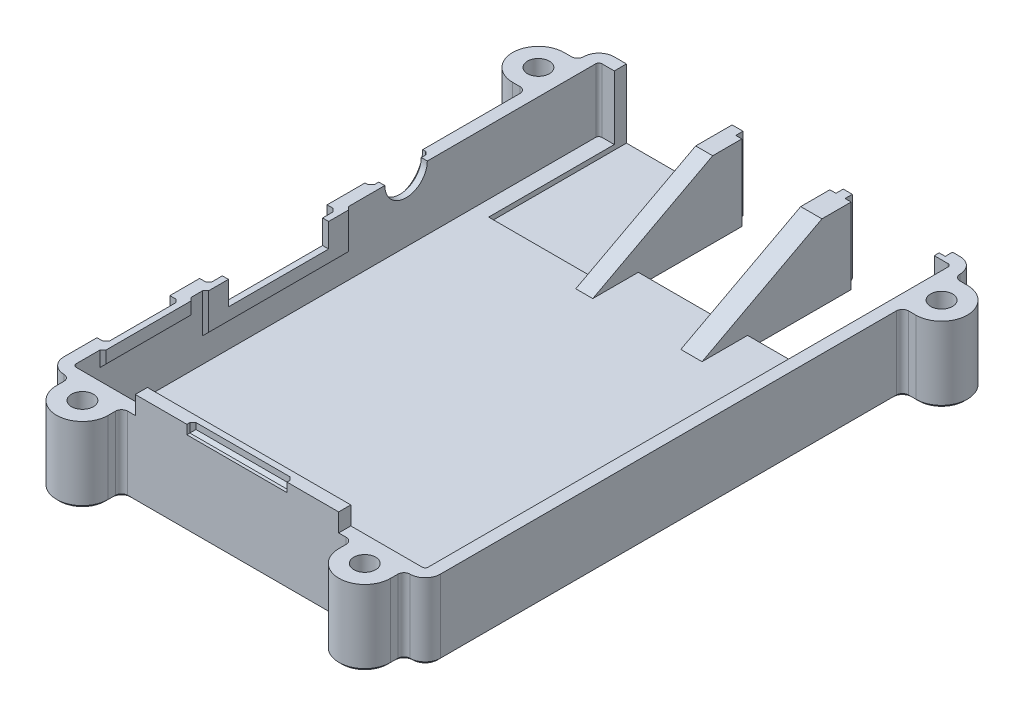
SolidWorks part; units mm, degrees
ref_plane "Front Plane" through (0, 0, 0) normal (0, 0, 1) x (1, 0, 0)
ref_plane "Top Plane" through (0, 0, 0) normal (0, 1, 0) x (1, 0, 0)
ref_plane "Right Plane" through (0, 0, 0) normal (1, 0, 0) x (0, 0, -1)
sketch "Sketch2" plane through (0, 0, 0) normal (0, 1, 0) x (1, 0, 0)
  line L1 (2.5, 0) -> (59.5, 0)
  line L2 (0, 2.5) -> (0, 88.1)
  line L3 (2.5, 90.6) -> (59.5, 90.6)
  line L4 (62, 2.5) -> (62, 88.1)
  arc A0 (0, 2.5) -> (2.5, 0) centre (2.5, 2.5) ccw
  arc A1 (59.5, 0) -> (62, 2.5) centre (59.5, 2.5) ccw
  arc A2 (62, 88.1) -> (59.5, 90.6) centre (59.5, 88.1) ccw
  arc A3 (2.5, 90.6) -> (0, 88.1) centre (2.5, 88.1) ccw
  point P7 (0, 0)
  point P10 (62, 0)
  point P13 (62, 90.6)
  point P16 (0, 90.6)
  dimension "D3" = 2.5
  dimension "D1" = 62
  dimension "D2" = 90.6
extrude "Base" add sketch "Sketch2" along normal blind 12.5
shell "Shell" thickness 2 removed face at (31, 12.5, -45.3)
sketch "Sketch14" plane through (0, 0, 0) normal (0, -1, 0) x (1, 0, 0)
  line L0 (31, 0) -> (31, -90.6) construction
  line L2 (59.5, -90.6) -> (2.5, -90.6) construction
  line L3 (-2.2, -78.6) -> (0, -78.6)
  line L4 (0, -88.1) -> (0, -2.5) construction
  line L5 (0, -78.6) -> (0, -87.1)
  line L6 (0, -87.1) -> (-2.2, -87.1)
  line L7 (3.5, 2.2) -> (3.5, 0)
  line L8 (2.5, 0) -> (59.5, 0) construction
  line L9 (3.5, 0) -> (12, 0)
  line L10 (12, 0) -> (12, 2.2)
  line L11 (64.2, -78.6) -> (62, -78.6)
  line L12 (62, -87.1) -> (64.2, -87.1)
  line L13 (62, -78.6) -> (62, -87.1)
  line L14 (50, 0) -> (50, 2.2)
  line L15 (58.5, 0) -> (50, 0)
  line L16 (58.5, 2.2) -> (58.5, 0)
  line L17 (2.5, 0) -> (59.5, 0) construction
  arc A0 (-2.2, -78.6) -> (-2.2, -87.1) centre (-2.2, -82.85) ccw
  arc A1 (3.5, 2.2) -> (12, 2.2) centre (7.75, 2.2) cw
  arc A2 (64.2, -78.6) -> (64.2, -87.1) centre (64.2, -82.85) cw
  arc A3 (58.5, 2.2) -> (50, 2.2) centre (54.25, 2.2) ccw
  dimension "D1" = 2.2
  dimension "D2" = 8.5
  dimension "D3" = 3.5
  dimension "D4" = 3.5
extrude "Clamps" add sketch "Sketch14" against normal up to surface (12.5 mm away) up to face at (31, 12.5, -45.3)
fillet "Clamp Fillets" radius 1 8 edges at (50, 6.25, 0) (58.5, 6.25, 0) (12, 6.25, 0) (3.5, 6.25, 0) (0, 6.25, -87.1) (0, 6.25, -78.6) (62, 6.25, -78.6) (62, 6.25, -87.1)
sketch "Sketch20" plane through (0, 0, 0) normal (0, -1, 0) x (1, 0, 0)
  circle A0 centre (7.75, 2.2) radius 1.8
  circle A1 centre (54.25, 2.2) radius 1.8
  circle A2 centre (64.2, -82.85) radius 1.8
  circle A3 centre (-2.2, -82.85) radius 1.8
  arc A4 (12, 2.2) -> (3.5, 2.2) centre (7.75, 2.2) ccw construction
  arc A5 (58.5, 2.2) -> (50, 2.2) centre (54.25, 2.2) ccw construction
  arc A6 (-2.2, -78.6) -> (-2.2, -87.1) centre (-2.2, -82.85) ccw construction
  arc A7 (64.2, -87.1) -> (64.2, -78.6) centre (64.2, -82.85) ccw construction
  dimension "D1" = 3.6
extrude "Clamp Holes" cut sketch "Sketch20" against normal through all
sketch "Sketch21" plane through (0, 0, 0) normal (0, -1, 0) x (1, 0, 0)
  circle A0 centre (7.75, 2.2) radius 2.9
  circle A1 centre (54.25, 2.2) radius 2.9
  circle A2 centre (64.2, -82.85) radius 2.9
  circle A3 centre (-2.2, -82.85) radius 2.9
  circle A4 centre (-2.2, -82.85) radius 1.8 construction
  circle A5 centre (7.75, 2.2) radius 1.8 construction
  circle A6 centre (54.25, 2.2) radius 1.8 construction
  circle A7 centre (64.2, -82.85) radius 1.8 construction
  dimension "D1" = 5.8
extrude "Clamp Countersinks" cut sketch "Sketch21" against normal blind 3.4
chamfer "Clamp Countersink Chamfers" distance 0.3 angle 45 4 edges at (-2.2, 0, -85.75) (64.2, 0, -85.75) (54.25, 0, -0.7) (7.75, 0, -0.7)
sketch "Sketch22" plane through (0, 12.5, 0) normal (0, 1, 0) x (1, 0, 0)
  line L0 (31, 2) -> (31, 0) construction
  line L1 (2.5, 2) -> (59.5, 2) construction
  line L2 (13, 0) -> (49, 0) construction
  line L4 (14.25, 2) -> (47.75, 2)
  line L5 (14.25, 2) -> (14.25, 0)
  line L6 (14.25, 0) -> (47.75, 0)
  line L7 (47.75, 2) -> (47.75, 0)
  dimension "D1" = 16.75
  dimension "D2" = 33.5
extrude "SD Fill" add sketch "Sketch22" along normal blind 3
sketch "Sketch23" plane through (0, 0, 0) normal (0, 0, 1) x (1, 0, 0)
  line L0 (31, 15.5) -> (31, 0) construction
  line L1 (14.25, 15.5) -> (47.75, 15.5) construction
  line L2 (13, 0) -> (49, 0) construction
  line L4 (22.75, 15.5) -> (39.25, 15.5)
  line L5 (22.75, 15.5) -> (22.75, 14)
  line L6 (22.75, 14) -> (39.25, 14)
  line L7 (39.25, 15.5) -> (39.25, 14)
  dimension "D1" = 8.25
  dimension "D2" = 16.5
  dimension "D3" = 1.5
extrude "SD Approach" cut sketch "Sketch23" against normal blind 1
chamfer "SD Approach Chamfer" distance 0.5 angle 45 3 edges at (39.25, 14.75, -1) (31, 14, -1) (22.75, 14.75, -1)
sketch "Sketch24" plane through (0, 0, -90.6) normal (0, 0, -1) x (-1, 0, 0)
  line L0 (-59.5, 12.5) -> (-2.5, 12.5) construction
  line L1 (-57.25, 12.5) -> (-42.75, 12.5)
  line L2 (-57.25, 12.5) -> (-57.25, 0)
  line L3 (-57.25, 0) -> (-42.75, 0)
  line L4 (-42.75, 12.5) -> (-42.75, 0)
  line L5 (-59.5, 0) -> (-2.5, 0) construction
  line L6 (0, 12.5) -> (0, 0) construction
  line L7 (-39.25, 12.5) -> (-24.75, 12.5)
  line L8 (-39.25, 12.5) -> (-39.25, 0)
  line L9 (-39.25, 0) -> (-24.75, 0)
  line L10 (-24.75, 12.5) -> (-24.75, 0)
  dimension "D1" = 14.5
  dimension "D2" = 24.75
  dimension "D3" = 42.75
extrude "USB Cutout" cut sketch "Sketch24" against normal blind 18.25
sketch "Sketch25" plane through (0, 0, -90.6) normal (0, 0, -1) x (-1, 0, 0)
  line L0 (-42.75, 12.5) -> (-39.25, 12.5) construction
  line L1 (-41.75, 12.5) -> (-58.25, 12.5)
  line L2 (-41.75, 12.5) -> (-41.75, 0)
  line L3 (-41.75, 0) -> (-58.25, 0)
  line L4 (-58.25, 12.5) -> (-58.25, 0)
  line L5 (-59.5, 0) -> (-57.25, 0) construction
  line L6 (-24.75, 12.5) -> (-2.5, 12.5) construction
  line L7 (-23.75, 12.5) -> (-40.25, 12.5)
  line L8 (-23.75, 12.5) -> (-23.75, 0)
  line L9 (-23.75, 0) -> (-40.25, 0)
  line L10 (-40.25, 12.5) -> (-40.25, 0)
  line L11 (-42.75, 0) -> (-39.25, 0) construction
  line L12 (-57.25, 12.5) -> (-57.25, 0) construction
  line L13 (-42.75, 0) -> (-42.75, 12.5) construction
  line L14 (-39.25, 12.5) -> (-39.25, 0) construction
  line L15 (-24.75, 0) -> (-24.75, 12.5) construction
  point P18 (-57.25, 6.25)
  dimension "D1" = 1
  dimension "D2" = 1
  dimension "D3" = 1
  dimension "D4" = 1
extrude "USB Approach" cut sketch "Sketch25" against normal blind 1.2
sketch "Sketch26" plane through (42.75, 0, 0) normal (1, 0, 0) x (0, 0, -1)
  line L0 (88.6, 2) -> (88.6, 12.5)
  line L1 (88.6, 12.5) -> (84.6, 12.5)
  line L2 (88.6, 2) -> (64.8524, 2)
  line L3 (64.8524, 2) -> (84.6, 12.5)
  line L4 (90.6, 0) -> (90.6, 12.5) construction
  dimension "D1" = 6
  dimension "D2" = 28
extrude "USB Inner Support" add sketch "Sketch26" against normal up to surface (3.5 mm away) up to face at (39.25, 4.8333, -83.45)
sketch "Sketch27" plane through (24.75, 0, 0) normal (1, 0, 0) x (0, 0, -1)
  line L0 (88.6, 2) -> (88.6, 12.5)
  line L1 (88.6, 12.5) -> (84.6, 12.5)
  line L2 (88.6, 2) -> (64.8524, 2)
  line L3 (64.8524, 2) -> (84.6, 12.5)
  line L4 (90.6, 0) -> (90.6, 12.5) construction
  dimension "D1" = 6
  dimension "D2" = 28
extrude "USB Outer Support" add sketch "Sketch27" against normal blind 2.8
sketch "Sketch28" plane through (0, 0, -90.6) normal (0, 0, -1) x (-1, 0, 0)
  line L0 (-23.75, 12.5) -> (-2.5, 12.5) construction
  line L1 (-21.95, 12.5) -> (-4.55, 12.5)
  line L2 (-21.95, 12.5) -> (-21.95, 1.2)
  line L3 (-21.95, 1.2) -> (-4.55, 1.2)
  line L4 (-4.55, 12.5) -> (-4.55, 1.2)
  line L5 (0, 12.5) -> (0, 0) construction
  dimension "D1" = 17.4
  dimension "D2" = 4.55
  dimension "D3" = 11.3
extrude "RJ45 Cutout" cut sketch "Sketch28" against normal blind 22.7
sketch "Sketch29" plane through (2, 0, 0) normal (1, 0, 0) x (0, 0, -1)
  line L0 (88.1, 12.5) -> (2.5, 12.5) construction
  line L1 (6.45, 12.5) -> (21.45, 12.5)
  line L2 (6.45, 12.5) -> (6.45, 10)
  line L3 (6.45, 10) -> (21.45, 10)
  line L4 (21.45, 12.5) -> (21.45, 10)
  line L5 (0, 12.5) -> (0, 0) construction
  line L6 (23.35, 12.5) -> (47.35, 12.5)
  line L7 (23.35, 12.5) -> (23.35, 6.07)
  line L8 (23.35, 6.07) -> (47.35, 6.07)
  line L9 (47.35, 12.5) -> (47.35, 6.07)
  dimension "D1" = 24
  dimension "D2" = 15
  dimension "D3" = 6.45
  dimension "D4" = 23.35
  dimension "D5" = 2.5
  dimension "D6" = 6.43
extrude "HDMI Support" add sketch "Sketch29" along normal blind 0.5
chamfer "HDMI Support Chamfer" distance 0.5 angle 45 6 edges at (2.5, 9.285, -47.35) (2.5, 6.07, -35.35) (2.5, 9.285, -23.35) (2.5, 11.25, -21.45) (2.5, 10, -13.95) (2.5, 11.25, -6.45)
sketch "Sketch30" plane through (0, 0, 0) normal (-1, 0, 0) x (0, 0, 1)
  line L0 (-77.6, 12.5) -> (-2.5, 12.5) construction
  line L1 (-24.85, 12.5) -> (-45.85, 12.5)
  line L2 (-24.85, 12.5) -> (-24.85, 6.57)
  line L3 (-24.85, 6.57) -> (-45.85, 6.57)
  line L4 (-45.85, 12.5) -> (-45.85, 6.57)
  line L5 (0, 12.5) -> (0, 0) construction
  line L6 (-19.95, 12.5) -> (-7.95, 12.5)
  line L7 (-19.95, 12.5) -> (-19.95, 10.5)
  line L8 (-19.95, 10.5) -> (-7.95, 10.5)
  line L9 (-7.95, 12.5) -> (-7.95, 10.5)
  dimension "D1" = 12
  dimension "D2" = 21
  dimension "D3" = 7.95
  dimension "D4" = 24.85
  dimension "D5" = 5.93
  dimension "D6" = 2
extrude "HDMI Approach" cut sketch "Sketch30" against normal blind 1.5
sketch "Sketch31" plane through (1.5, 0, 0) normal (-1, 0, 0) x (0, 0, 1)
  line L0 (-24.85, 12.5) -> (-45.85, 12.5) construction
  line L1 (-43.6, 12.5) -> (-27.1, 12.5)
  line L2 (-43.6, 12.5) -> (-43.6, 8.57)
  line L3 (-43.6, 8.57) -> (-27.1, 8.57)
  line L4 (-27.1, 12.5) -> (-27.1, 8.57)
  line L5 (-45.85, 12.5) -> (-45.85, 6.57) construction
  line L6 (-24.85, 6.57) -> (-24.85, 12.5) construction
  line L7 (-45.85, 6.57) -> (-24.85, 6.57) construction
  dimension "D1" = 2.25
  dimension "D2" = 2.25
  dimension "D3" = 2
extrude "HDMI Cutout" cut sketch "Sketch31" against normal blind 1
chamfer "HDMI Approach Chamfer" distance 0.5 angle 45 6 edges at (1.5, 11.5, -7.95) (1.5, 10.5, -13.95) (1.5, 11.5, -19.95) (1.5, 9.535, -24.85) (1.5, 6.57, -35.35) (1.5, 9.535, -45.85)
sketch "Sketch32" plane through (0, 0, 0) normal (-1, 0, 0) x (0, 0, 1)
  line L0 (-77.6, 12.5) -> (-45.85, 12.5) construction
  line L1 (0, 12.5) -> (0, 0) construction
  circle A0 centre (-56.85, 12.5) radius 3.5
  dimension "D1" = 7
  dimension "D2" = 56.85
extrude "Audio Cutout" cut sketch "Sketch32" against normal blind 2
sketch "Sketch33" plane through (0, 0, 0) normal (-1, 0, 0) x (0, 0, 1)
  circle A0 centre (-56.85, 12.5) radius 4.75
  arc A1 (-60.35, 12.5) -> (-53.35, 12.5) centre (-56.85, 12.5) ccw construction
  dimension "D1" = 9.5
extrude "Audio Approach" cut sketch "Sketch33" against normal blind 1
chamfer "Audio Approach Chamfer" distance 0.5 angle 45 1 edges at (1, 7.75, -56.85)
sketch "Sketch34" plane through (0, 0, 0) normal (0, -1, 0) x (1, 0, 0)
  line L0 (62, -2.5) -> (62, -77.6) construction
  line L1 (52.5, -9.4) -> (58.5, -9.4)
  line L2 (52.5, -9.4) -> (52.5, -62.1)
  line L3 (52.5, -62.1) -> (58.5, -62.1)
  line L4 (58.5, -9.4) -> (58.5, -62.1)
  line L5 (13, 0) -> (49, 0) construction
  point P6 (55.5, -9.4)
  dimension "D1" = 6
  dimension "D2" = 52.7
  dimension "D3" = 3.5
  dimension "D4" = 9.4
extrude "Header Cutout" cut sketch "Sketch34" against normal blind 2
sketch "Sketch35" plane through (0, 0, 0) normal (0, -1, 0) x (1, 0, 0)
  line L0 (55.5, -9.4) -> (55.5, -62.1) construction
  line L1 (58.5, -9.4) -> (52.5, -9.4) construction
  line L2 (52.5, -62.1) -> (58.5, -62.1) construction
  line L3 (52.5, -35.75) -> (58.5, -35.75) construction
  line L4 (52.5, -9.4) -> (52.5, -62.1) construction
  line L5 (58.5, -62.1) -> (58.5, -9.4) construction
  line L6 (56, -9.4) -> (55, -9.4)
  line L7 (55, -9.4) -> (55, -10.4)
  line L8 (55, -10.4) -> (53.5, -10.4)
  line L9 (53.5, -10.4) -> (53.5, -15.3625)
  line L10 (53.5, -15.3625) -> (52.5, -15.3625)
  line L11 (52.5, -15.3625) -> (52.5, -16.3625)
  line L12 (52.5, -16.3625) -> (53.5, -16.3625)
  line L13 (53.5, -16.3625) -> (53.5, -28.2875)
  line L14 (53.5, -28.2875) -> (52.5, -28.2875)
  line L15 (52.5, -28.2875) -> (52.5, -29.2875)
  line L16 (52.5, -29.2875) -> (53.5, -29.2875)
  line L17 (53.5, -29.2875) -> (53.5, -34.25)
  line L18 (53.5, -34.25) -> (55, -34.25)
  line L19 (55, -34.25) -> (55, -35.25)
  line L20 (55, -35.25) -> (52.5, -35.25)
  line L21 (52.5, -35.25) -> (52.5, -36.25)
  line L22 (56, -62.1) -> (55, -62.1)
  line L23 (55, -36.25) -> (52.5, -36.25)
  line L24 (55, -37.25) -> (55, -36.25)
  line L25 (53.5, -37.25) -> (55, -37.25)
  line L26 (53.5, -42.2125) -> (53.5, -37.25)
  line L27 (52.5, -42.2125) -> (53.5, -42.2125)
  line L28 (52.5, -43.2125) -> (52.5, -42.2125)
  line L29 (53.5, -43.2125) -> (52.5, -43.2125)
  line L30 (53.5, -55.1375) -> (53.5, -43.2125)
  line L31 (52.5, -55.1375) -> (53.5, -55.1375)
  line L32 (52.5, -56.1375) -> (52.5, -55.1375)
  line L33 (53.5, -56.1375) -> (52.5, -56.1375)
  line L34 (53.5, -61.1) -> (53.5, -56.1375)
  line L35 (55, -61.1) -> (53.5, -61.1)
  line L36 (55, -62.1) -> (55, -61.1)
  line L37 (56, -62.1) -> (56, -61.1)
  line L38 (56, -61.1) -> (57.5, -61.1)
  line L39 (57.5, -61.1) -> (57.5, -56.1375)
  line L40 (57.5, -56.1375) -> (58.5, -56.1375)
  line L41 (58.5, -56.1375) -> (58.5, -55.1375)
  line L42 (58.5, -55.1375) -> (57.5, -55.1375)
  line L43 (57.5, -55.1375) -> (57.5, -43.2125)
  line L44 (57.5, -43.2125) -> (58.5, -43.2125)
  line L45 (58.5, -43.2125) -> (58.5, -42.2125)
  line L46 (58.5, -42.2125) -> (57.5, -42.2125)
  line L47 (57.5, -42.2125) -> (57.5, -37.25)
  line L48 (57.5, -37.25) -> (56, -37.25)
  line L49 (56, -37.25) -> (56, -36.25)
  line L50 (56, -36.25) -> (58.5, -36.25)
  line L51 (58.5, -35.25) -> (58.5, -36.25)
  line L52 (56, -35.25) -> (58.5, -35.25)
  line L53 (56, -34.25) -> (56, -35.25)
  line L54 (57.5, -34.25) -> (56, -34.25)
  line L55 (57.5, -29.2875) -> (57.5, -34.25)
  line L56 (58.5, -29.2875) -> (57.5, -29.2875)
  line L57 (58.5, -28.2875) -> (58.5, -29.2875)
  line L58 (57.5, -28.2875) -> (58.5, -28.2875)
  line L59 (57.5, -16.3625) -> (57.5, -28.2875)
  line L60 (58.5, -16.3625) -> (57.5, -16.3625)
  line L61 (58.5, -15.3625) -> (58.5, -16.3625)
  line L62 (57.5, -15.3625) -> (58.5, -15.3625)
  line L63 (57.5, -10.4) -> (57.5, -15.3625)
  line L64 (56, -10.4) -> (57.5, -10.4)
  line L65 (56, -9.4) -> (56, -10.4)
  dimension "D1" = 0.5
  dimension "D2" = 1
  dimension "D3" = 1.5
  dimension "D4" = 11.925
extrude "Header Cover" add sketch "Sketch35" against normal blind 1
chamfer "Shell Chamfer" distance 0.5 angle 45 46 edges at (41, 0, -90.6) (58.875, 0, -90.6) (61.2678, 0, -89.8678) (62.2929, 0, -87.3929) (63.6, 0, -87.1) (68.45, 0, -82.85) (63.6, 0, -78.6) (62.2929, 0, -78.3071) (13.125, 0, -90.6) (0.7322, 0, -89.8678) (-0.2929, 0, -87.3929) (-1.6, 0, -87.1) (-6.45, 0, -82.85) (-1.6, 0, -78.6) (-0.2929, 0, -78.3071) (0, 0, -40.05) (0.7322, 0, -0.7322) (3.2071, 0, 0.2929) (3.5, 0, 1.6) (7.75, 0, 6.45) (12, 0, 1.6) (12.2929, 0, 0.2929) (31, 0, 0) (49.7071, 0, 0.2929) (50, 0, 1.6) (54.25, 0, 6.45) (58.5, 0, 1.6) (58.7929, 0, 0.2929) (61.2678, 0, -0.7322) (62, 0, -40.05) (52.5, 0, -12.3812) (53.75, 0, -9.4) (57.25, 0, -9.4) (58.5, 0, -12.3812) (52.5, 0, -22.325) (58.5, 0, -22.325) (58.5, 0, -32.2687) (52.5, 0, -32.2687) (52.5, 0, -39.2312) (58.5, 0, -39.2312) (58.5, 0, -49.175) (52.5, 0, -49.175) (58.5, 0, -59.1187) (57.25, 0, -62.1) (52.5, 0, -59.1188) (53.75, 0, -62.1)
